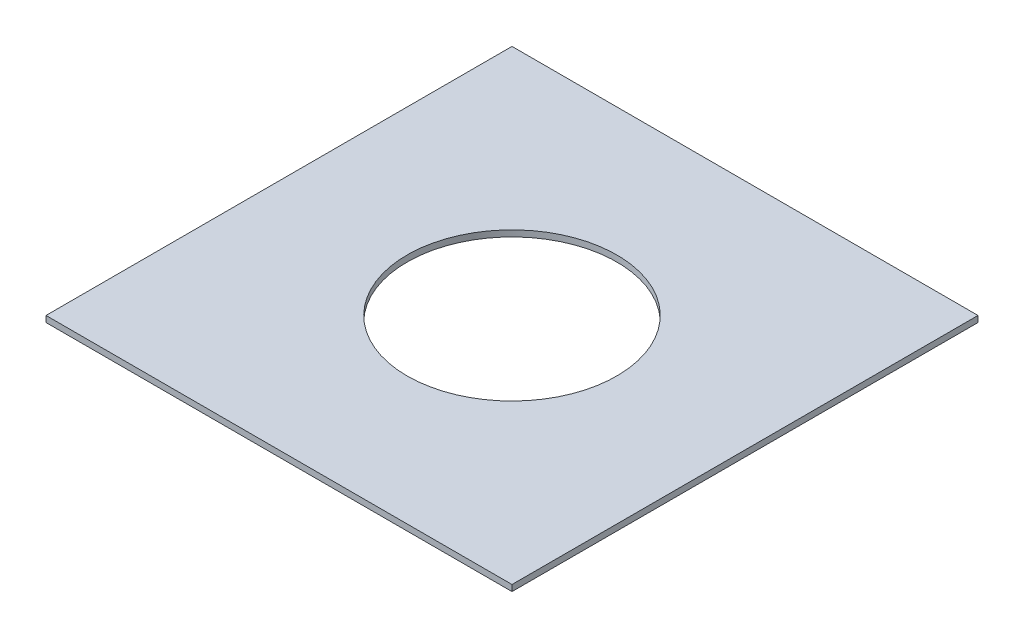
SolidWorks part; units mm, degrees
material "PTFE (general)"
ref_plane "Front Plane" through (0, 0, 0) normal (0, 0, 1) x (1, 0, 0)
ref_plane "Top Plane" through (0, 0, 0) normal (0, 1, 0) x (1, 0, 0)
ref_plane "Right Plane" through (0, 0, 0) normal (1, 0, 0) x (0, 0, -1)
sketch "Sketch1" plane through (0, 0, 0) normal (0, 1, 0) x (1, 0, 0)
  line L0 (17.5573, 16.4499) -> (17.5573, -43.5501) construction
  line L9 (17.5573, -43.5501) -> (77.5573, -43.5501) construction
  line L10 (77.5573, -43.5501) -> (77.5573, 16.4499) construction
  line L11 (17.5573, 16.4499) -> (77.5573, 16.4499) construction
  line L12 (17.5573, 16.4499) -> (17.5573, -43.5501)
  line L13 (17.5573, -43.5501) -> (77.5573, -43.5501)
  line L14 (77.5573, -43.5501) -> (77.5573, 16.4499)
  line L16 (17.5573, 16.4499) -> (77.5573, 16.4499)
  circle A2 centre (47.5573, -13.5501) radius 13.5
  circle A3 centre (47.5573, -13.5501) radius 13.5
  dimension "D1" = 0
extrude "Boss-Extrude1" add sketch "Sketch1" along normal blind 0.7937
